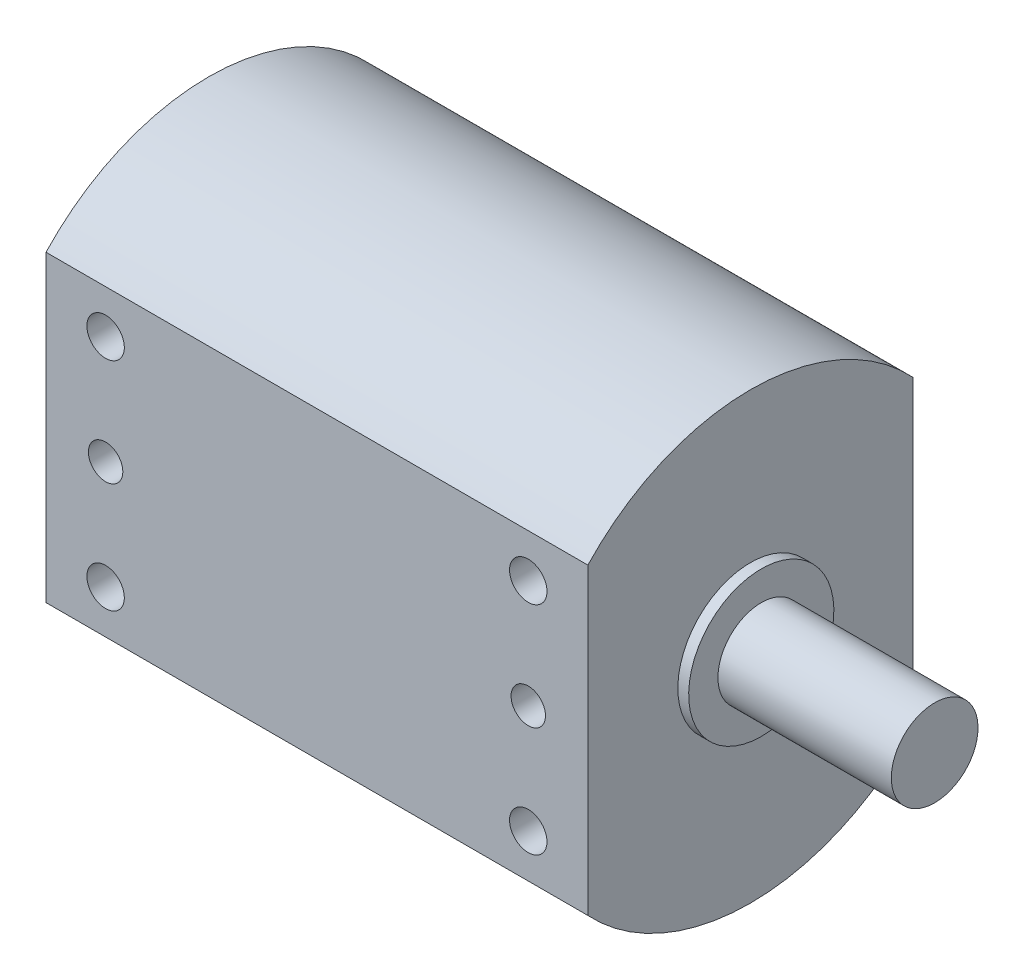
SolidWorks part; units mm, degrees
material "AISI 316 Annealed Stainless Steel Bar (SS)"
ref_plane "Front Plane" through (0, 0, 0) normal (0, 0, 1) x (1, 0, 0)
ref_plane "Top Plane" through (0, 0, 0) normal (0, 1, 0) x (1, 0, 0)
ref_plane "Right Plane" through (0, 0, 0) normal (1, 0, 0) x (0, 0, -1)
sketch "Sketch1" plane through (0, 0, 0) normal (1, 0, 0) x (0, 0, -1)
  line L0 (0, 20.5183) -> (0, 0)
  line L1 (-15, -14) -> (15, -14)
  line L2 (-15, -14) -> (-15, 14)
  line L3 (-15, 14) -> (15, 14)
  line L4 (15, -14) -> (15, 14)
  line L5 (-15, -14) -> (15, 14) construction
  line L6 (-15, 14) -> (15, -14) construction
  circle A0 centre (0, 0) radius 20.5183
  dimension "D1" = 30
  dimension "D2" = 28
sketch "Sketch2" plane through (0, 0, 0) normal (0, 0, 1) x (1, 0, 0)
  line L0 (-34, 0) -> (42, 0)
  line L1 (42, 0) -> (42, 4)
  line L2 (42, 4) -> (26, 4)
  line L3 (25, 6.7) -> (25, 20.5183)
  line L4 (25, 20.5183) -> (-25, 20.5183)
  line L5 (-25, 20.5183) -> (-25, 6.7)
  line L6 (-27.5, 4) -> (-34, 4)
  line L7 (-34, 4) -> (-34, 0)
  line L10 (26, 4) -> (26, 6.7)
  line L11 (26, 6.7) -> (25, 6.7)
  line L12 (-25, 6.7) -> (-27.5, 6.7)
  line L13 (-27.5, 6.7) -> (-27.5, 4)
  dimension "D1" = 4
  dimension "D2" = 2.5
  dimension "D3" = 42
  dimension "D4" = 50
  dimension "D5" = 6.7
  dimension "D6" = 9
  dimension "D7" = 1
revolve "Revolve1" add sketch "Sketch2" angle 360 about L0
sketch "Sketch3" plane through (-25, 0, 0) normal (-1, 0, 0) x (0, 0, 1)
  line L2 (15, -14) -> (15, 14) construction
  line L3 (-15, 20.5183) -> (15, 20.5183)
  line L4 (-15, 20.5183) -> (-15, -20.5183)
  line L5 (-15, -20.5183) -> (15, -20.5183)
  line L6 (15, 20.5183) -> (15, -20.5183)
  line L7 (-15, -14) -> (-15, 14) construction
  circle A0 centre (0, 0) radius 20.5183 construction
extrude "Cut-Extrude1" cut sketch "Sketch3" against normal through all both and the other way through all flip side to cut
hole_wizard "#8-32 Tapped Hole1" positions "Sketch4" profile "Sketch5" tap size "#8-32" standard "ANSI Inch"
sketch "Sketch4" plane through (0, 0, -15) normal (0, 0, -1) x (-1, 0, 0)
  line L1 (-19.5, 10) -> (19.5, 10)
  line L2 (-19.5, 10) -> (-19.5, -10)
  line L3 (-19.5, -10) -> (19.5, -10)
  line L4 (19.5, 10) -> (19.5, -10)
  line L6 (-25, 14) -> (-25, -14) construction
  line L7 (-19.5, 0) -> (0, 0) construction
  line L8 (0, 0) -> (0, 10) construction
  point P1 (-19.5, 10)
  point P2 (19.5, -10)
  point P53 (-19.5, -10)
  point P54 (19.5, 10)
  dimension "D1" = 5.5
  dimension "D2" = 20
sketch "Sketch5" plane through (19.5, 10, -15) normal (1, 0, 0) x (0, 1, 0)
  line L0 (0, 0) -> (0, 11.7478)
  line L1 (0, 11.7478) -> (1.7272, 10.71)
  line L2 (1.7272, 10.71) -> (1.7272, 0)
  line L5 (1.7272, 0) -> (0, 0)
  line L10 (0, 11.7478) -> (-1.7272, 10.71) construction
  line L11 (0, -6.35) -> (0, 107.95) construction
  dimension "Tap Drill Dia." = 3.4544
  dimension "Tap Drill Depth" = 10.71
  dimension "Drill Angle" = 118
cosmetic thread "Hole Thread1" parameters "D1"=8.33, "D2"=4.1656
cosmetic thread "Hole Thread2" parameters "D1"=8.33, "D2"=4.1656
cosmetic thread "Hole Thread3" parameters "D1"=8.33, "D2"=4.1656
cosmetic thread "Hole Thread4" parameters "D1"=8.33, "D2"=4.1656
hole_wizard "1/8 (0.1250) Dowel Hole1" positions "Sketch6" profile "Sketch7" hole size "1/8" standard "ANSI Inch"
sketch "Sketch6" plane through (0, 0, -15) normal (0, 0, -1) x (-1, 0, 0)
  line L0 (-19.5, 10) -> (-19.5, -10) construction
  line L1 (19.5, 10) -> (19.5, -10) construction
  point P0 (-19.5, 0)
  point P2 (19.5, 0)
sketch "Sketch7" plane through (19.5, 0, -15) normal (1, 0, 0) x (0, 1, 0)
  line L0 (0, 0) -> (0, 6.9539)
  line L1 (0, 6.9539) -> (1.5875, 6)
  line L2 (1.5875, 6) -> (1.5875, 0)
  line L5 (1.5875, 0) -> (0, 0)
  line L10 (0, 6.9539) -> (-1.5875, 6) construction
  line L11 (0, -6.35) -> (0, 107.95) construction
  dimension "Hole Dia." = 3.175
  dimension "Hole Depth" = 6
  dimension "Drill Angle" = 118
mirror "Mirror1" about plane through (0, 0, 0) normal (0, 0, 1) of "1/8 (0.1250) Dowel Hole1", "#8-32 Tapped Hole1"
cosmetic thread "Hole Thread5" parameters "D1"=8.33, "D2"=4.1656
cosmetic thread "Hole Thread6" parameters "D1"=8.33, "D2"=4.1656
cosmetic thread "Hole Thread7" parameters "D1"=8.33, "D2"=4.1656
cosmetic thread "Hole Thread8" parameters "D1"=8.33, "D2"=4.1656
hole_wizard "#8-32 Tapped Hole2" positions "Sketch8" profile "Sketch10" tap size "#8-32" standard "ANSI Inch"
sketch "Sketch8" plane through (-34, 0, 0) normal (-1, 0, 0) x (0, 0, 1)
  point P0 (0, 0)
sketch "Sketch10" plane through (-34, 0, 0) normal (0, 1, 0) x (0, 0, 1)
  line L0 (0, 0) -> (0, 11.7478)
  line L1 (0, 11.7478) -> (1.7272, 10.71)
  line L2 (1.7272, 10.71) -> (1.7272, 0)
  line L5 (1.7272, 0) -> (0, 0)
  line L10 (0, 11.7478) -> (-1.7272, 10.71) construction
  line L11 (0, -6.35) -> (0, 107.95) construction
  dimension "Tap Drill Dia." = 3.4544
  dimension "Tap Drill Depth" = 10.71
  dimension "Drill Angle" = 118
cosmetic thread "Hole Thread9"
